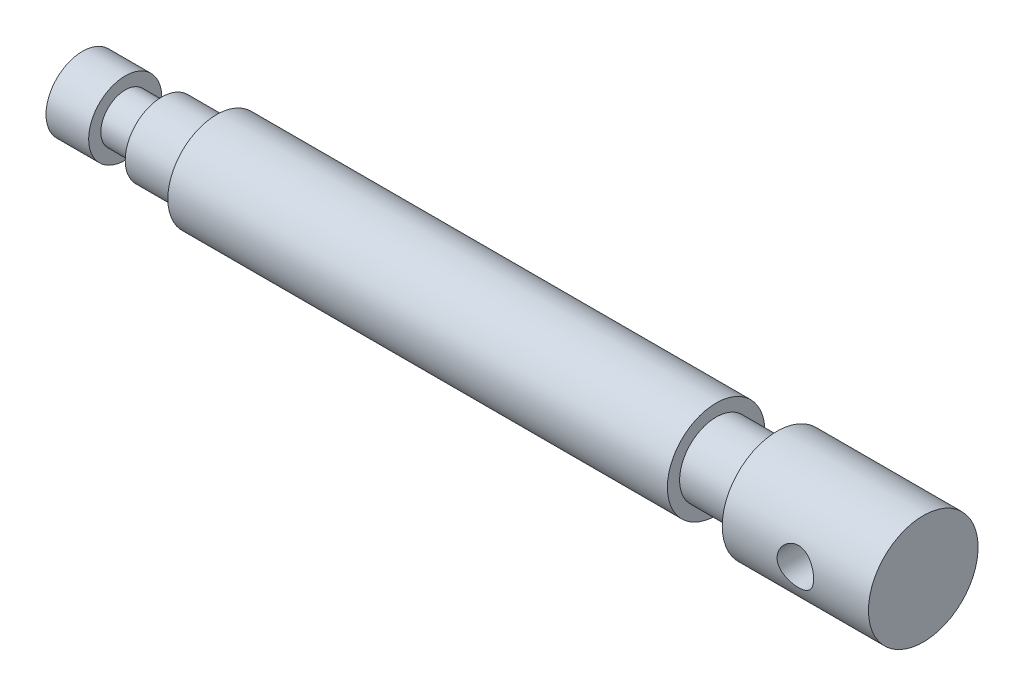
SolidWorks part; units mm, degrees
ref_plane "Front Plane" through (0, 0, 0) normal (0, 0, 1) x (1, 0, 0)
ref_plane "Top Plane" through (0, 0, 0) normal (0, 1, 0) x (1, 0, 0)
ref_plane "Right Plane" through (0, 0, 0) normal (1, 0, 0) x (0, 0, -1)
sketch "Sketch2" plane through (0, 0, 0) normal (0, 0, 1) x (1, 0, 0)
  line L0 (0, 0) -> (138, 0)
  line L1 (0, 0) -> (0, 6)
  line L2 (0, 6) -> (7, 6)
  line L3 (7, 6) -> (7, 4)
  line L4 (7, 4) -> (13, 4)
  line L5 (13, 4) -> (13, 6)
  line L6 (13, 6) -> (22, 6)
  line L7 (22, 6) -> (22, 8)
  line L8 (22, 8) -> (104, 8)
  line L9 (104, 8) -> (104, 6)
  line L10 (104, 6) -> (114, 6)
  line L11 (114, 6) -> (114, 9)
  line L12 (114, 9) -> (138, 9)
  line L13 (138, 9) -> (138, 0)
  circle A0 centre (126, 0) radius 3
  dimension "D12" = 6
  dimension "D1" = 138
  dimension "D2" = 6
  dimension "D3" = 7
  dimension "D4" = 6
  dimension "D5" = 4
  dimension "D6" = 82
  dimension "D7" = 8
  dimension "D8" = 6
  dimension "D9" = 10
  dimension "D10" = 24
  dimension "D11" = 9
  dimension "D13" = 12
revolve "Revolve1" add sketch "Sketch2" angle 360 about L0 region at (71.9119, 3.9446, 0)
extrude "Cut-Extrude1" cut sketch "Sketch2<3>" against normal through all and the other way through all contours L0 A0 | L0 A0 region at (126, -1.2732, 0) region at (126, 1.2732, 0)
sketch "Sketch2<3>" plane through (0, 0, 0) normal (0, 0, 1) x (1, 0, 0) same geometry as "Sketch2"
